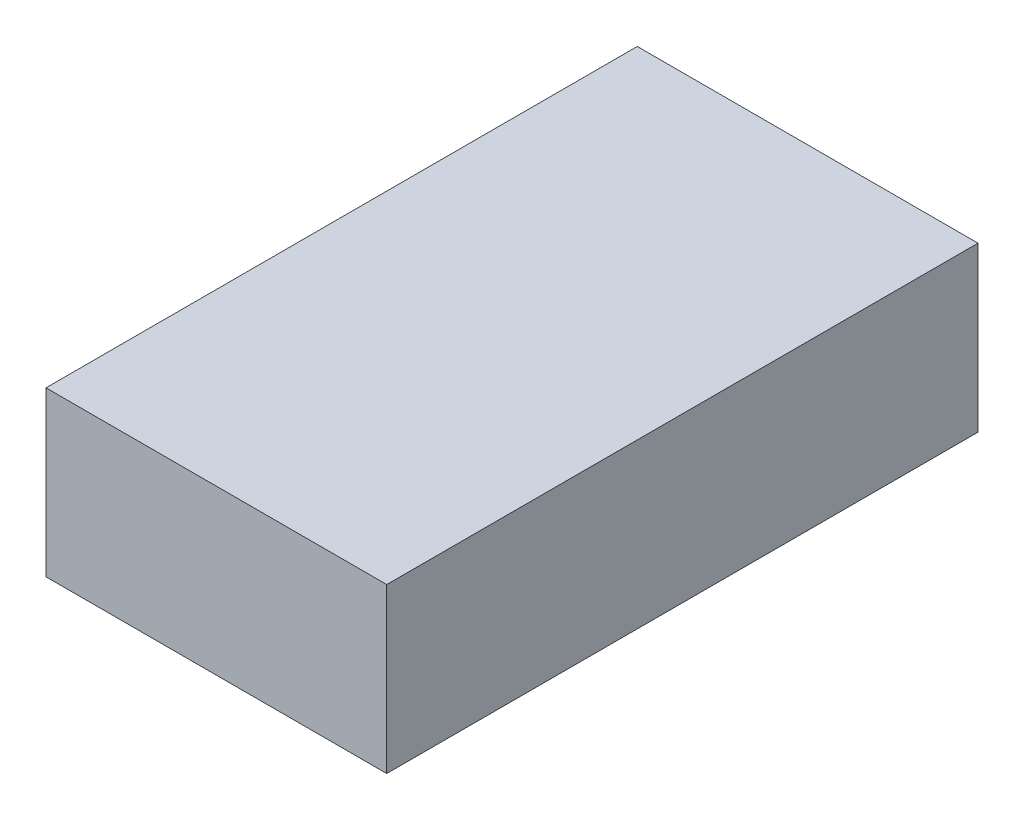
SolidWorks part; units mm, degrees
ref_plane "Front Plane" through (0, 0, 0) normal (0, 0, 1) x (1, 0, 0)
ref_plane "Top Plane" through (0, 0, 0) normal (0, 1, 0) x (1, 0, 0)
ref_plane "Right Plane" through (0, 0, 0) normal (1, 0, 0) x (0, 0, -1)
sketch "Sketch1" plane through (0, 0, 0) normal (0, 1, 0) x (1, 0, 0)
  line L1 (-51, -88.5) -> (51, -88.5)
  line L2 (-51, -88.5) -> (-51, 88.5)
  line L3 (-51, 88.5) -> (51, 88.5)
  line L4 (51, -88.5) -> (51, 88.5)
  line L5 (-51, -88.5) -> (51, 88.5) construction
  line L6 (-51, 88.5) -> (51, -88.5) construction
  point P0 (0, 0)
  dimension "D1" = 177
  dimension "D2" = 102
extrude "Boss-Extrude1" add sketch "Sketch1" along normal blind 49
